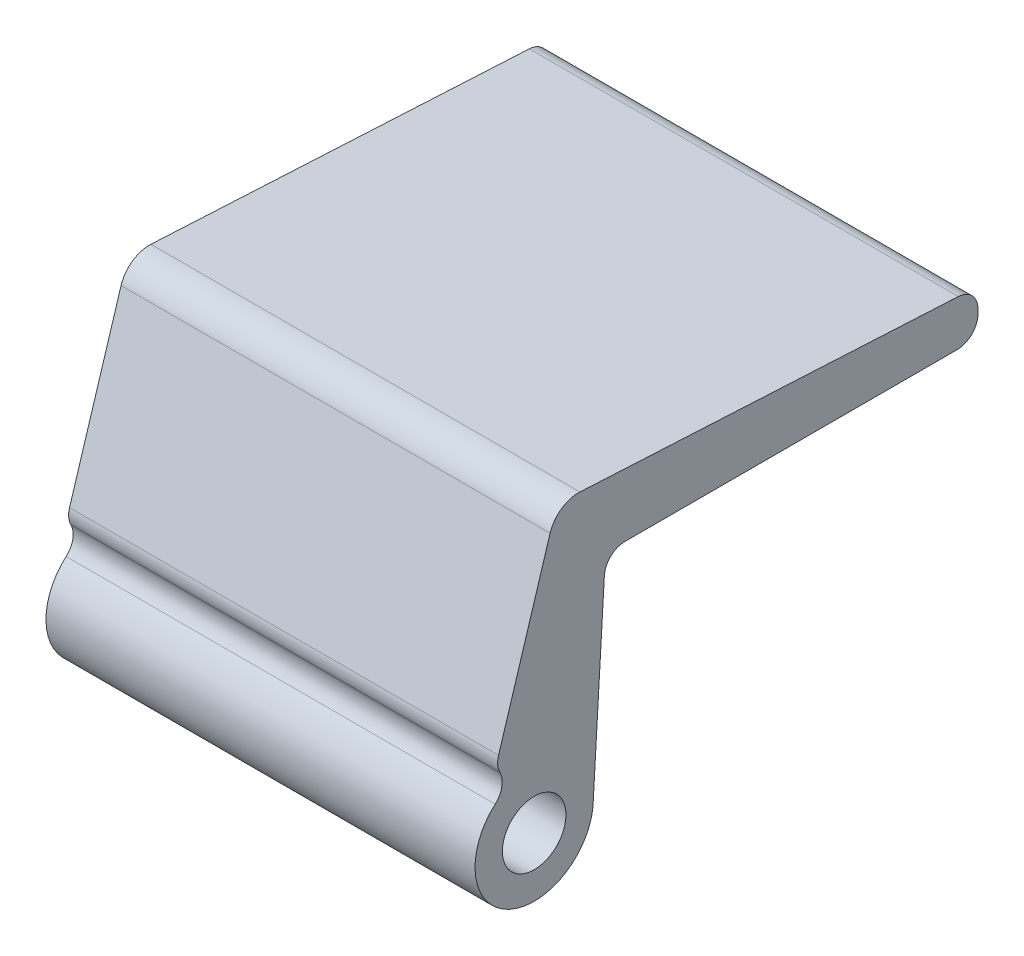
SolidWorks part; units mm, degrees
ref_plane "Front Plane" through (0, 0, 0) normal (0, 0, 1) x (1, 0, 0)
ref_plane "Top Plane" through (0, 0, 0) normal (0, 1, 0) x (1, 0, 0)
ref_plane "Right Plane" through (0, 0, 0) normal (1, 0, 0) x (0, 0, -1)
sketch "Sketch1" plane through (0, 0, 0) normal (1, 0, 0) x (0, 0, -1)
  line L30 (1.536, 18.5) -> (-2.5722, 5.2199)
  line L33 (30, 17) -> (30, 16)
  line L34 (-2.5722, 5.2199) -> (-1.7681, 3.588)
  line L35 (4.8214, 14) -> (4, 0)
  line L37 (4.9388, 14) -> (4.8214, 14)
  line L40 (4.9388, 14) -> (30, 14)
  line L41 (30, 16) -> (30, 14)
  line L42 (30, 17) -> (1.536, 18.5)
  circle A5 centre (0, 0) radius 2.15
  arc A8 (-1.7681, 3.588) -> (4, 0) centre (0, 0) ccw
extrude "Boss-Extrude1" add sketch "Sketch1" along normal mid plane 29
fillet "Fillet1" radius 2 1 edges at (0, 18.5, -1.536)
fillet "Fillet2" radius 1.4 5 edges at (0, 3.588, 1.7681) (0, 5.2199, 2.5722) (0, 14, -30) (0, 14, -4.8214) (0, 17, -30)
